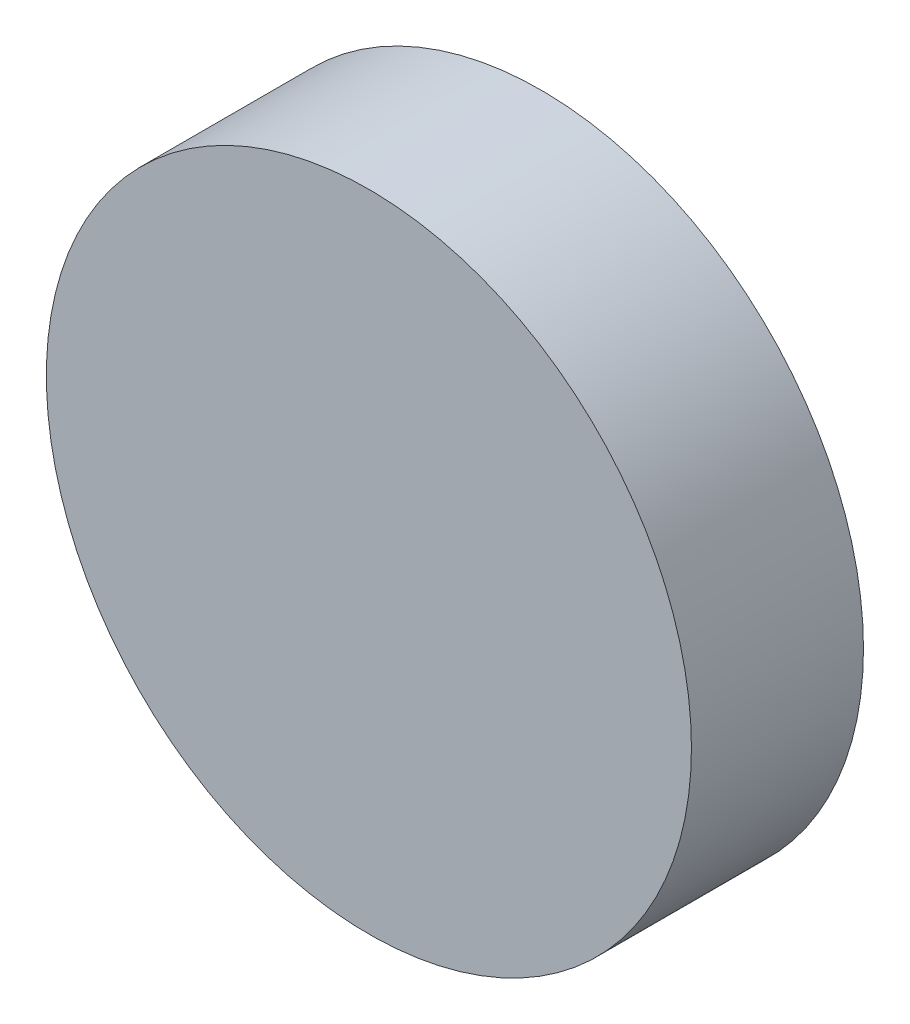
SolidWorks part; units mm, degrees
ref_plane "Front Plane" through (0, 0, 0) normal (0, 0, 1) x (1, 0, 0)
ref_plane "Top Plane" through (0, 0, 0) normal (0, 1, 0) x (1, 0, 0)
ref_plane "Right Plane" through (0, 0, 0) normal (1, 0, 0) x (0, 0, -1)
sketch "Sketch1" plane through (0, 0, 0) normal (0, 0, 1) x (1, 0, 0)
  circle A0 centre (0, 0) radius 37.5
  dimension "D1" = 75
extrude "Boss-Extrude1" add sketch "Sketch1" along normal blind 20
ref_axis "Axis1" through (0, 0, 20) along (0, 0, -1)
